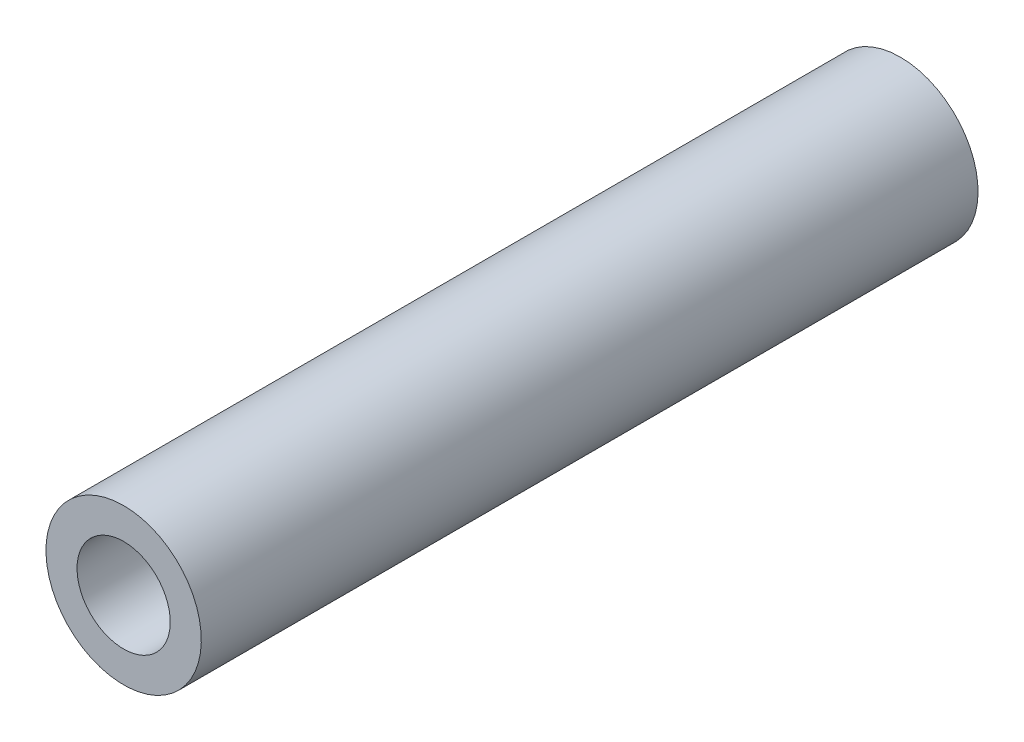
SolidWorks part; units mm, degrees
material "Plain Carbon Steel"
ref_plane "Front Plane" through (0, 0, 0) normal (0, 0, 1) x (1, 0, 0)
ref_plane "Top Plane" through (0, 0, 0) normal (0, 1, 0) x (1, 0, 0)
ref_plane "Right Plane" through (0, 0, 0) normal (1, 0, 0) x (0, 0, -1)
sketch "Sketch1" plane through (0, 0, 0) normal (1, 0, 0) x (0, 0, -1)
  line L0 (10, 0) -> (10, 3)
  line L1 (10, 3) -> (0, 3)
  line L2 (0, 3) -> (0, 5)
  line L3 (0, 5) -> (50, 5)
  line L4 (50, 5) -> (50, 3)
  line L5 (50, 3) -> (40, 3)
  line L6 (40, 3) -> (40, 0)
  line L7 (40, 0) -> (10, 0)
  dimension "D1" = 50
  dimension "D2" = 5
  dimension "D3" = 3
  dimension "D4" = 10
revolve "Revolve1" add sketch "Sketch1" angle 360 about L7
